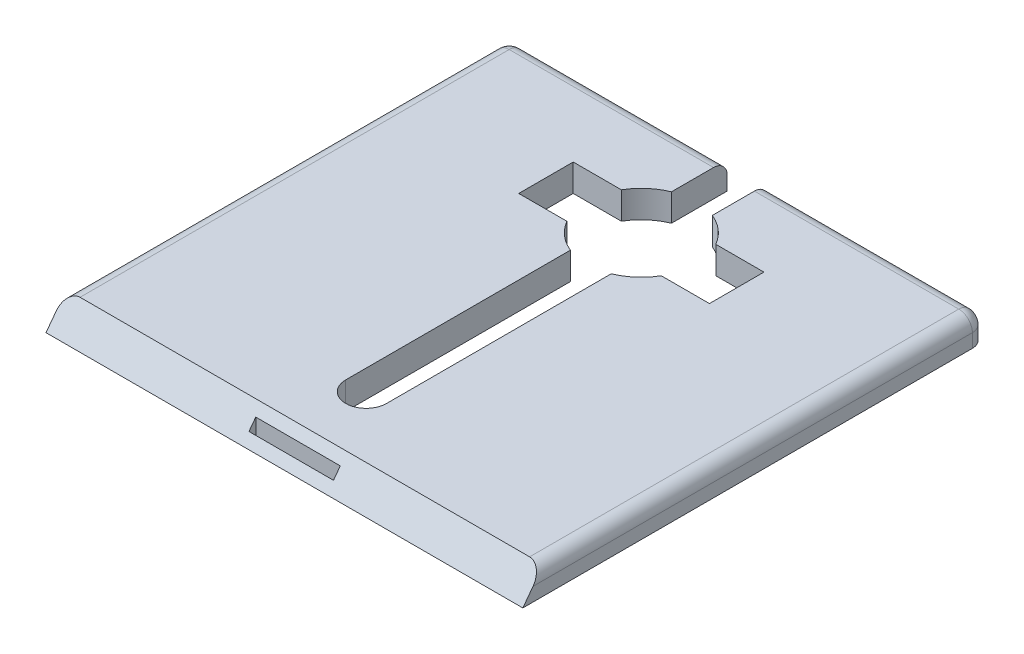
SolidWorks part; units mm, degrees
ref_plane "Ebene vorne" through (0, 0, 0) normal (0, 0, 1) x (1, 0, 0)
ref_plane "Ebene oben" through (0, 0, 0) normal (0, 1, 0) x (1, 0, 0)
ref_plane "Ebene rechts" through (0, 0, 0) normal (1, 0, 0) x (0, 0, -1)
sketch "Skizze1" plane through (0, 0, 0) normal (0, 1, 0) x (1, 0, 0)
  line L1 (-8.75, -8.5) -> (8.75, -8.5)
  line L2 (-8.75, -8.5) -> (-8.75, 8.5)
  line L3 (-8.75, 8.5) -> (8.75, 8.5)
  line L4 (8.75, -8.5) -> (8.75, 8.5)
  line L5 (-8.75, -8.5) -> (8.75, 8.5) construction
  line L6 (-8.75, 8.5) -> (8.75, -8.5) construction
  point P0 (0, 0)
  dimension "D1" = 17
  dimension "D2" = 17.5
extrude "Aufsatz-Linear austragen1" add sketch "Skizze1" along normal blind 1
fillet "Verrundung1" radius 0.5 3 edges at (8.75, 1, 0) (0, 1, -8.5) (-8.75, 1, 0)
sketch "Skizze2" plane through (-8.75, 0, 0) normal (-1, 0, 0) x (0, 0, 1)
  line L0 (8.5, 0) -> (7.75, 1)
  line L1 (-8, 1) -> (8.5, 1) construction
  line L2 (7.75, 1) -> (8.5, 1)
  line L3 (8.5, 1) -> (8.5, 0)
  dimension "D1" = 0.75
extrude "Schnitt-Linear austragen1" cut sketch "Skizze2" against normal up to surface (17.5 mm away) up to face at (8.75, 0.25, 0)
fillet "Verrundung2" radius 0.5 4 edges at (8.6036, 0.8536, -8.3536) (-8.6036, 0.8536, -8.3536) (8.75, 0.25, -8.5) (-8.75, 0.25, -8.5)
sketch "Skizze5" plane through (0, 1, 0) normal (0, 1, 0) x (1, 0, 0)
  line L0 (-8.75, 8) -> (-8.75, -8.5) construction
  line L1 (-3.5, 3.6) -> (3.5, 3.6)
  line L2 (-3.5, 3.6) -> (-3.5, 5.6)
  line L3 (-3.5, 5.6) -> (3.5, 5.6)
  line L4 (3.5, 3.6) -> (3.5, 5.6)
  line L5 (-3.5, 3.6) -> (3.5, 5.6) construction
  line L6 (-3.5, 5.6) -> (3.5, 3.6) construction
  line L7 (-8.25, 8.5) -> (8.25, 8.5) construction
  circle A0 centre (0, 4.6) radius 2
  dimension "D2" = 4
  dimension "D1" = 7
  dimension "D3" = 2
  dimension "D4" = 8.75
  dimension "D5" = 3.9
extrude "Schlüsselloch" cut sketch "Skizze5" against normal up to surface (1 mm away) contours A0 L3 L2 L1 | L3 A0 | L1 A0 L3 | L1 A0 | A0 L1 L4 L3 region at (-2.7046, 1, -4.6) region at (0, 1, -4.6) region at (0, 1, -3.19) region at (2.7046, 1, -4.6) region at (0, 1, -6.01) up to face at (0, 0, -2.7012)
sketch "Skizze6" plane through (0, 1, 0) normal (0, 1, 0) x (1, 0, 0)
  line L0 (8.25, -7.75) -> (-8.25, -7.75) construction
  line L1 (-1.5515, -8.25) -> (1.5515, -8.25)
  line L2 (-1.5515, -8.25) -> (-1.5515, -8)
  line L3 (-1.5515, -8) -> (1.5515, -8)
  line L4 (1.5515, -8.25) -> (1.5515, -8)
  line L5 (-1.5515, -8.25) -> (1.5515, -8) construction
  line L6 (-1.5515, -8) -> (1.5515, -8.25) construction
  line L7 (-8.75, -8.125) -> (-8.75, -8.5) construction
  point P0 (0, -8.125)
  dimension "D1" = 0.25
  dimension "D2" = 0.25
  dimension "D3" = 8.75
extrude "Griff" cut sketch "Skizze6" against normal up to surface (1 mm away) up to face at (0, 0, -4.6)
sketch "Skizze7" plane through (0, 1, 0) normal (0, 1, 0) x (1, 0, 0)
  line L5 (0, 8.5) -> (0, -5.5) construction
  line L6 (-8.25, 8.5) -> (8.25, 8.5) construction
  line L7 (0.75, 8.5) -> (0.75, -5.5)
  line L8 (-0.75, 8.5) -> (-0.75, -5.5)
  arc A0 (0.75, 8.5) -> (-0.75, 8.5) centre (0, 8.5) ccw
  arc A1 (-0.75, -5.5) -> (0.75, -5.5) centre (0, -5.5) ccw
  point P4 (0, 1.5)
  dimension "D1" = 14
  dimension "D2" = 1.5
extrude "Langloch_Antenne" cut sketch "Skizze7" against normal up to surface (1 mm away) up to face at (0, 0, 8.125)
